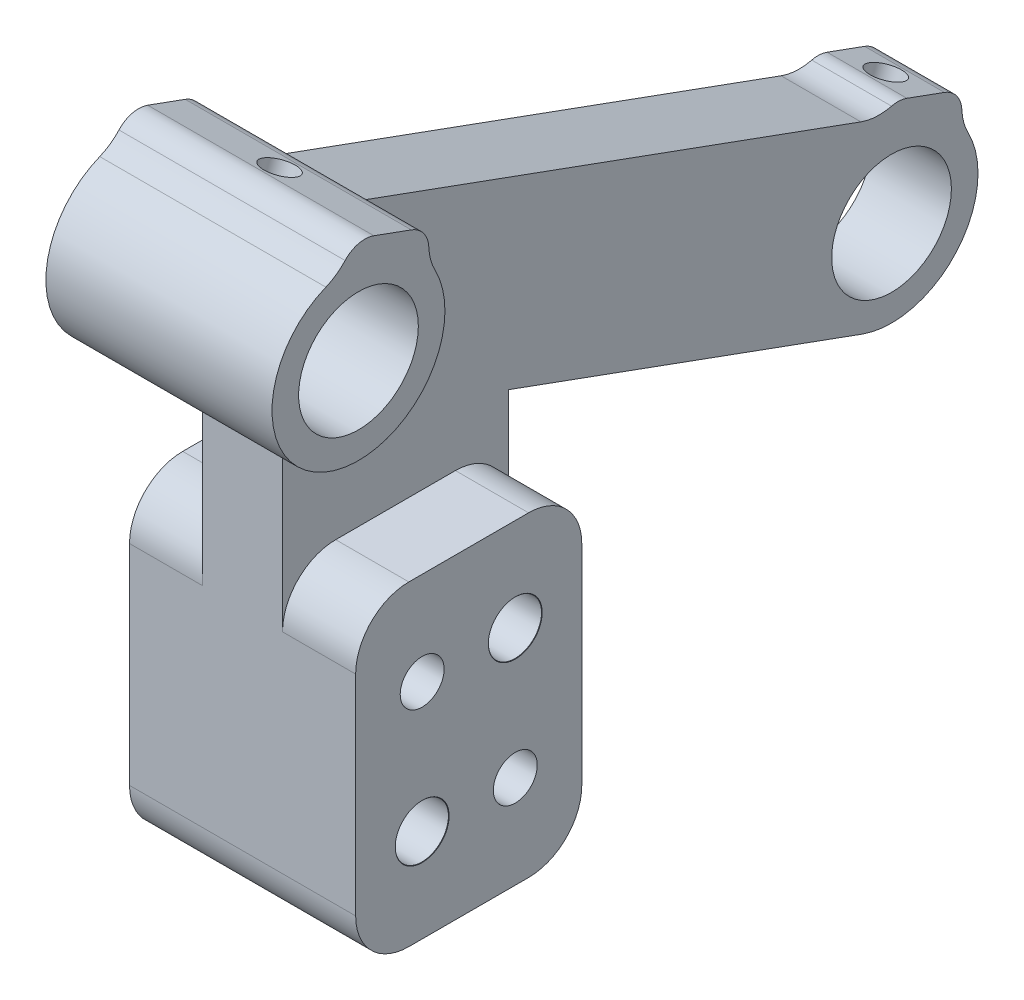
SolidWorks part; units mm, degrees
note: The reader was unsure of these and kept them because the rebuilt part matched: shared geometry of "Sketch2<4>", "Sketch2<5>".
material "5052-H32"
ref_plane "Front Plane" through (0, 0, 0) normal (0, 0, 1) x (1, 0, 0)
ref_plane "Top Plane" through (0, 0, 0) normal (0, 1, 0) x (1, 0, 0)
ref_plane "Right Plane" through (0, 0, 0) normal (1, 0, 0) x (0, 0, -1)
sketch "Sketch2" plane through (0, 0, 0) normal (1, 0, 0) x (0, 0, -1)
  line L2 (-6, -4.7333) -> (20.5644, -14.402)
  line L3 (26.7622, -1.7593) -> (23.9432, -0.7333)
  line L4 (20.4845, -0.5386) -> (-17.5273, 13.2966)
  line L5 (-18.8129, 14.8287) -> (-21.6319, 15.8547)
  line L6 (-6, -12) -> (-6, -27.7468)
  line L7 (-10, -31.7468) -> (-19, -31.7468)
  line L8 (-23, -27.7468) -> (-23, -12)
  line L9 (-23, -12) -> (-23, 1.7975)
  line L10 (-6, -4.7333) -> (-6, -12)
  line L11 (-19, -8) -> (-10, -8)
  arc A0 (20.5644, -14.402) -> (28.5358, -5.2595) centre (22.7875, -8.294) ccw
  circle A1 centre (22.7875, -8.294) radius 6.5 construction
  arc A2 (28.5358, -5.2595) -> (28.0765, -3.5565) centre (32.0731, -3.3922) cw
  arc A3 (28.0765, -3.5565) -> (28.5358, -5.2595) centre (32.0731, -3.3922) ccw construction
  arc A4 (28.0765, -3.5565) -> (26.7622, -1.7593) centre (26.0782, -3.6387) ccw
  arc A5 (28.0765, -3.5565) -> (26.7622, -1.7593) centre (26.0782, -3.6387) ccw construction
  arc A6 (23.9432, -0.7333) -> (22.7903, -0.6684) centre (23.2591, -2.6126) ccw
  arc A7 (23.9432, -0.7333) -> (22.7903, -0.6684) centre (23.2591, -2.6126) ccw construction
  arc A8 (22.7903, -0.6684) -> (20.4845, -0.5386) centre (21.8526, 3.2202) cw
  arc A9 (20.4845, -0.5386) -> (22.7903, -0.6684) centre (21.8526, 3.2202) ccw construction
  circle A11 centre (-22.7875, 8.294) radius 6.5 construction
  arc A12 (-17.4986, 13.0315) -> (-18.8129, 14.8287) centre (-19.4969, 12.9493) ccw
  arc A13 (-17.4986, 13.0315) -> (-18.8129, 14.8287) centre (-19.4969, 12.9493) ccw construction
  arc A14 (-21.6319, 15.8547) -> (-23.7939, 15.3228) centre (-22.316, 13.9753) ccw
  arc A15 (-21.6319, 15.8547) -> (-23.7939, 15.3228) centre (-22.316, 13.9753) ccw construction
  arc A16 (-23.7939, 15.3228) -> (-25.2404, 14.3134) centre (-26.7499, 18.0177) cw
  arc A17 (-25.2404, 14.3134) -> (-23.7939, 15.3228) centre (-26.7499, 18.0177) ccw construction
  circle A20 centre (22.7875, -8.294) radius 4.5
  circle A21 centre (22.7875, -8.294) radius 4.5 construction
  circle A22 centre (-22.7875, 8.294) radius 4.5
  circle A23 centre (-22.7875, 8.294) radius 4.5 construction
  arc A24 (-25.2404, 14.3134) -> (-17.0393, 11.3285) centre (-22.7875, 8.294) ccw
  arc A26 (-6, -27.7468) -> (-10, -31.7468) centre (-10, -27.7468) cw
  arc A27 (-10, -31.7468) -> (-6, -27.7468) centre (-10, -27.7468) ccw construction
  arc A28 (-19, -31.7468) -> (-23, -27.7468) centre (-19, -27.7468) cw
  arc A29 (-23, -27.7468) -> (-19, -31.7468) centre (-19, -27.7468) ccw construction
  arc A32 (-19, -8) -> (-23, -12) centre (-19, -12) ccw
  arc A33 (-19, -8) -> (-23, -12) centre (-19, -12) ccw construction
  arc A34 (-10, -8) -> (-6, -12) centre (-10, -12) cw
  arc A35 (-6, -12) -> (-10, -8) centre (-10, -12) ccw construction
  arc A38 (-17.4986, 13.0315) -> (-17.0393, 11.3285) centre (-13.502, 13.1958) ccw
  arc A40 (-17.4986, 13.0315) -> (-17.0393, 11.3285) centre (-13.502, 13.1958) ccw construction
extrude "Boss-Extrude1" add sketch "Sketch2" against normal up to vertex (3 mm away) and the other way up to vertex (3 mm away)
extrude "Boss-Extrude2" add sketch "Sketch2<4>" against normal up to vertex (8.5 mm away) and the other way up to vertex (8.5 mm away)
sketch "Sketch2<4>" plane through (0, 0, 0) normal (1, 0, 0) x (0, 0, -1) same geometry as "Sketch2"
extrude "Boss-Extrude3" add sketch "Sketch2<5>" against normal up to vertex (8.5 mm away) and the other way up to vertex (8.5 mm away)
sketch "Sketch2<5>" plane through (0, 0, 0) normal (1, 0, 0) x (0, 0, -1) same geometry as "Sketch2"
hole_wizard "M3 Tapped Hole1" positions "Sketch3" profile "Sketch5" tap size "M3" standard "ISO"
sketch "Sketch3" plane through (0, 7.0477, -2.5652) normal (0, 0.9397, -0.342) x (1, 0, 0)
  point P0 (0, -24.25)
sketch "Sketch5" plane through (0, 15.3417, 20.2224) normal (1, 0, 0) x (0, 0.342, 0.9397)
  line L0 (0, 0) -> (0, 3)
  line L1 (0, 3) -> (1.25, 3)
  line L2 (1.25, 3) -> (1.25, 0)
  line L5 (1.25, 0) -> (0, 0)
  line L11 (0, -6.35) -> (0, 107.95) construction
  dimension "Thru Tap Drill Dia." = 2.5
  dimension "Thru Tap Drill Depth" = 3
cosmetic thread "Hole Thread1" parameters "D2"=3
hole_wizard "M3 Tapped Hole2" positions "Sketch6" profile "Sketch7" tap size "M3" standard "ISO"
sketch "Sketch6" plane through (0, 7.0477, -2.5652) normal (0, 0.9397, -0.342) x (1, 0, 0)
  point P0 (0, 24.25)
sketch "Sketch7" plane through (0, -1.2463, -25.3527) normal (1, 0, 0) x (0, 0.342, 0.9397)
  line L0 (0, 0) -> (0, 3)
  line L1 (0, 3) -> (1.25, 3)
  line L2 (1.25, 3) -> (1.25, 0)
  line L5 (1.25, 0) -> (0, 0)
  line L11 (0, -6.35) -> (0, 107.95) construction
  dimension "Thru Tap Drill Dia." = 2.5
  dimension "Thru Tap Drill Depth" = 3
cosmetic thread "Hole Thread2" parameters "D2"=3
hole_wizard "M4 Tapped Hole1" positions "Sketch8" profile "Sketch10" tap size "M4" standard "ISO" end condition through all
sketch "Sketch8" plane through (-8.5, 0, 0) normal (-1, 0, 0) x (0, 0, 1)
  point P0 (18, -15)
  point P4 (11, -24.7468)
sketch "Sketch10" plane through (-8.5, -15, 18) normal (0, 1, 0) x (0, 0, 1)
  line L0 (0, 0) -> (0, 17)
  line L1 (0, 17) -> (1.65, 17)
  line L3 (1.65, 17) -> (1.65, 8)
  line L4 (2, 8) -> (1.65, 8)
  line L5 (2, 8) -> (2, 0.025)
  line L6 (2, 0.025) -> (2.025, 0)
  line L7 (2.025, 0) -> (0, 0)
  line L8 (-2, 0.025) -> (-2.025, 0) construction
  line L11 (0, -6.35) -> (0, 107.95) construction
  dimension "Thru Tap Drill Dia." = 3.3
  dimension "Thru Tap Drill Depth" = 17
  dimension "Thread Major Dia." = 4
  dimension "Thread Depth" = 8
  dimension "Near C'Sink Dia." = 4.05
  dimension "Near C'Sink Angle" = 90
hole_wizard "M5 Tapped Hole2" positions "Sketch11" profile "Sketch12" tap size "M4" standard "ISO" end condition through all
sketch "Sketch11" plane through (8.5, 0, 0) normal (1, 0, 0) x (0, 0, -1)
  point P0 (-11, -15)
  point P2 (-18, -24.7468)
sketch "Sketch12" plane through (8.5, -15, 11) normal (0, 1, 0) x (0, 0, -1)
  line L0 (0, 0) -> (0, 17)
  line L1 (0, 17) -> (1.65, 17)
  line L3 (1.65, 17) -> (1.65, 8)
  line L4 (2, 8) -> (1.65, 8)
  line L5 (2, 8) -> (2, 0.025)
  line L6 (2, 0.025) -> (2.025, 0)
  line L7 (2.025, 0) -> (0, 0)
  line L8 (-2, 0.025) -> (-2.025, 0) construction
  line L11 (0, -6.35) -> (0, 107.95) construction
  dimension "Thru Tap Drill Dia." = 3.3
  dimension "Thru Tap Drill Depth" = 17
  dimension "Thread Major Dia." = 4
  dimension "Thread Depth" = 8
  dimension "Near C'Sink Dia." = 4.05
  dimension "Near C'Sink Angle" = 90
